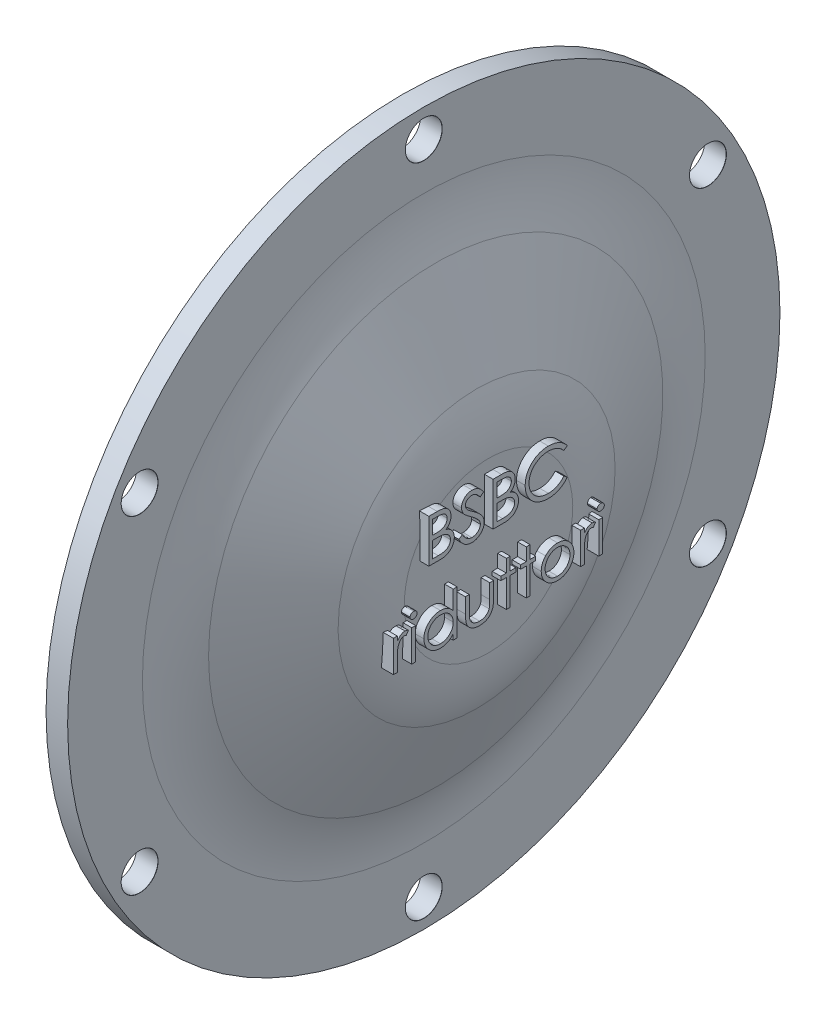
SolidWorks part; units mm, degrees
material "6061-T6 (SS)"
ref_plane "Piano frontale" through (0, 0, 0) normal (0, 0, 1) x (1, 0, 0)
ref_plane "Piano superiore" through (0, 0, 0) normal (0, 1, 0) x (1, 0, 0)
ref_plane "Piano destro" through (0, 0, 0) normal (1, 0, 0) x (0, 0, -1)
sketch "Schizzo4" plane through (0, 0, 0) normal (0, 0, 1) x (1, 0, 0)
  line L0 (0, 0) -> (0, 25)
  line L1 (0, 25) -> (-15, 57.5)
  line L2 (-15, 57.5) -> (-15, 82.5)
  line L3 (5, 0) -> (5, 26.0982)
  line L4 (5, 26.0982) -> (-10, 58.5982)
  line L5 (-10, 58.5982) -> (-10, 82.5)
  line L6 (-10, 82.5) -> (-15, 82.5)
  line L7 (5, 0) -> (0, 0)
  line L8 (-10, 0) -> (22.8769, 0) construction
  dimension "D1" = 82.5
  dimension "D2" = 15
  dimension "D3" = 35.7946
  dimension "D4" = 25
  dimension "D5" = 5
revolve "Rivoluzione2" add sketch "Schizzo4" angle 360 about L8
fillet "Raccordo4" radius 30 1 edges at (5, 0, 26.0982)
sketch "Schizzo5" plane through (-15, 0, 0) normal (-1, 0, 0) x (0, 0, 1)
  circle A0 centre (0, 0) radius 70
  circle A1 centre (0, 0) radius 67
  dimension "D1" = 140
  dimension "D2" = 134
extrude "Taglio-Estrusione1" cut sketch "Schizzo5" against normal blind 1.5
sketch "Schizzo6" plane through (-10, 0, 0) normal (1, 0, 0) x (0, 0, -1)
  point P0 (0, 76)
  dimension "D1" = 76
hole_wizard "Foro Ø8.5 (8.5)-1" positions "Schizzo7" profile "Schizzo8" hole size "Ø8.5" standard "ISO" end condition through all
sketch "Schizzo7" plane through (-10, 0, 0) normal (1, 0, 0) x (0, 0, -1)
  point P0 (0, 76)
sketch "Schizzo8" plane through (-10, 76, 0) normal (0, 1, 0) x (0, 0, -1)
  line L0 (0, 0) -> (0, 5)
  line L1 (0, 5) -> (4.25, 5)
  line L2 (4.25, 5) -> (4.25, 0.025)
  line L3 (4.25, 0.025) -> (4.275, 0)
  line L5 (4.275, 0) -> (0, 0)
  line L6 (-4.25, 0.025) -> (-4.275, 0) construction
  line L11 (0, -6.35) -> (0, 107.95) construction
  dimension "Thru Hole Dia." = 8.5
  dimension "Thru Hole Depth" = 5
  dimension "Near C'Sink Dia." = 8.55
  dimension "Near C'Sink Angle" = 90
pattern_circular "RipetizioneCircolare1" count 6 over 360 about axis through (-10, 0, 0) along (-1, 0, 0) of "Foro Ø8.5 (8.5)-1"
ref_plane "Piano1" through (7, 0, 0) normal (1, 0, 0) x (0, 0, -1)
sketch "Schizzo11" plane through (7, 0, 0) normal (1, 0, 0) x (0, 0, -1)
  text T0 "  BSBC\r\nriduttori" font "Century Gothic" height 10
extrude "Estrusione-Estrusione5" add sketch "Schizzo11" against normal up to surface (2.3758 mm away) up to face at (5, 0, 19.5091)
sketch "Schizzo12" plane through (-15, 0, 0) normal (-1, 0, 0) x (0, 0, 1)
  circle A0 centre (0, 0) radius 62.5
  circle A1 centre (0, 0) radius 57.5
  dimension "D1" = 125
  dimension "D2" = 115
extrude "Estrusione-Estrusione6" add sketch "Schizzo12" along normal blind 5
fillet "Raccordo5" radius 30 1 edges at (-10, 0, 58.5982)
chamfer "Smusso1" distance 1 angle 45 2 edges at (-20, 0, 57.5) (-20, 0, 62.5)
